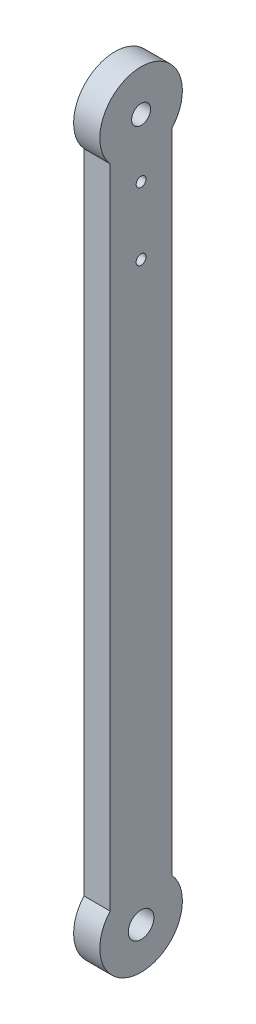
SolidWorks part; units mm, degrees
ref_plane "Front Plane" through (0, 0, 0) normal (0, 0, 1) x (1, 0, 0)
ref_plane "Top Plane" through (0, 0, 0) normal (0, 1, 0) x (1, 0, 0)
ref_plane "Right Plane" through (0, 0, 0) normal (1, 0, 0) x (0, 0, -1)
sketch "Sketch1" plane through (0, 0, 0) normal (1, 0, 0) x (0, 0, -1)
  line L0 (0, 0) -> (-3.75, -3.3072) construction
  line L2 (3.75, -3.3072) -> (3.75, -81.6928)
  line L3 (3.75, -81.6928) -> (-3.75, -81.6928) construction
  line L4 (-3.75, -3.3072) -> (-3.75, -81.6928)
  line L5 (3.75, -3.3072) -> (-3.75, -3.3072) construction
  line L6 (0, 0) -> (3.75, -3.3072) construction
  arc A1 (3.75, -3.3072) -> (-3.75, -3.3072) centre (0, 0) ccw
  arc A2 (-3.75, -81.6928) -> (3.75, -81.6928) centre (0, -85) ccw
  circle A3 centre (0, -85) radius 1.55
  circle A24 centre (0, -15.22) radius 0.6
  circle A264 centre (0, 0) radius 1.15
  circle A265 centre (0, -7.07) radius 0.6
  point P9 (0, 0)
  dimension "D1" = 2.3
  dimension "D2" = 10
  dimension "D4" = 10
  dimension "D6" = 3.1
  dimension "D7" = 1.2
  dimension "D3" = 7.5
  dimension "D5" = 85
  dimension "D8" = 8.15
  dimension "D9" = 7.07
extrude "Boss-Extrude3" add sketch "Sketch1" along normal blind 3.175
